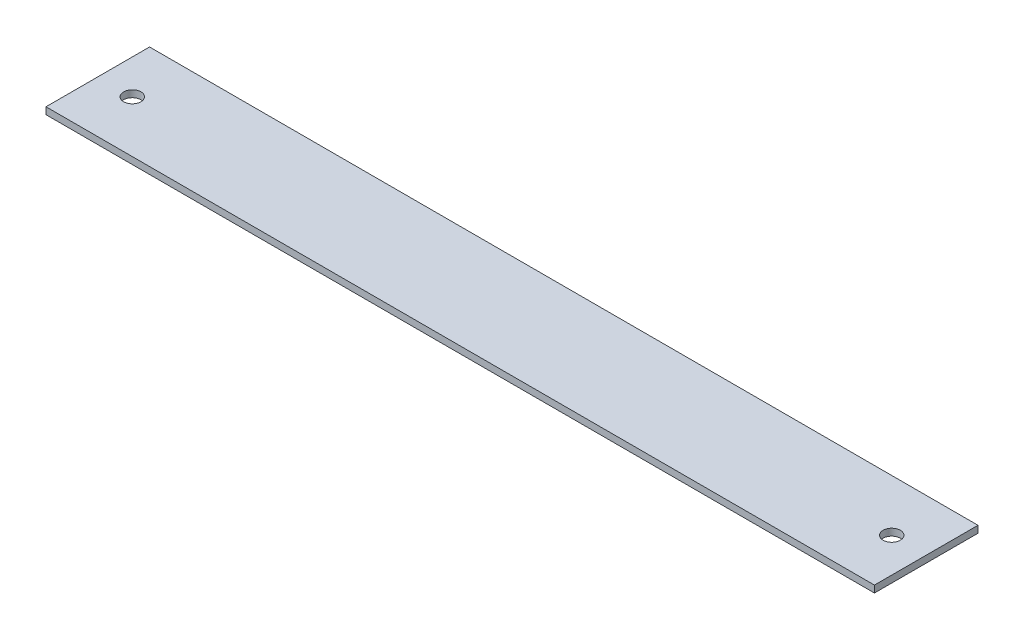
SolidWorks part; units mm, degrees
ref_plane "正面" through (0, 0, 0) normal (0, 0, 1) x (1, 0, 0)
ref_plane "平面" through (0, 0, 0) normal (0, 1, 0) x (1, 0, 0)
ref_plane "右側面" through (0, 0, 0) normal (1, 0, 0) x (0, 0, -1)
sketch "ｽｹｯﾁ1" plane through (0, 0, 0) normal (0, 1, 0) x (1, 0, 0)
  line L1 (0, 0) -> (120, 0)
  line L2 (0, 0) -> (0, 15)
  line L3 (0, 15) -> (120, 15)
  line L4 (120, 0) -> (120, 15)
  dimension "D1" = 15
  dimension "D2" = 120
extrude "ﾎﾞｽ - 押し出し1" add sketch "ｽｹｯﾁ1" along normal blind 1
hole_wizard "M3x0.5 ねじ穴1" positions "ｽｹｯﾁ2" profile "ｽｹｯﾁ3" tap size "M3x0.5" standard "JIS" end condition through all
sketch "ｽｹｯﾁ2" plane through (0, 1, 0) normal (0, 1, 0) x (1, 0, 0)
  line L0 (120, 15) -> (0, 15) construction
  line L1 (120, 0) -> (120, 15) construction
  line L2 (0, 15) -> (0, 0) construction
  point P0 (5, 7.5)
  point P2 (115, 7.5)
  point P11 (0, 7.5)
  dimension "D1" = 7.5
  dimension "D2" = 7.5
  dimension "D3" = 5
  dimension "D4" = 5
sketch "ｽｹｯﾁ3" plane through (5, 1, -7.5) normal (1, 0, 0) x (0, 0, 1)
  line L0 (0, 0) -> (0, 1)
  line L1 (0, 1) -> (1.25, 1)
  line L2 (1.25, 1) -> (1.25, 0)
  line L5 (1.25, 0) -> (0, 0)
  line L11 (0, -6.35) -> (0, 107.95) construction
  dimension "次ｻｰﾌｪｽまでのねじ下穴ﾄﾞﾘﾙ直径" = 2.5
  dimension "次ｻｰﾌｪｽまでのねじ下穴ﾄﾞﾘﾙの深さ" = 1
cosmetic thread "穴のねじ山1" parameters "D2"=3
cosmetic thread "穴のねじ山2" parameters "D2"=3
